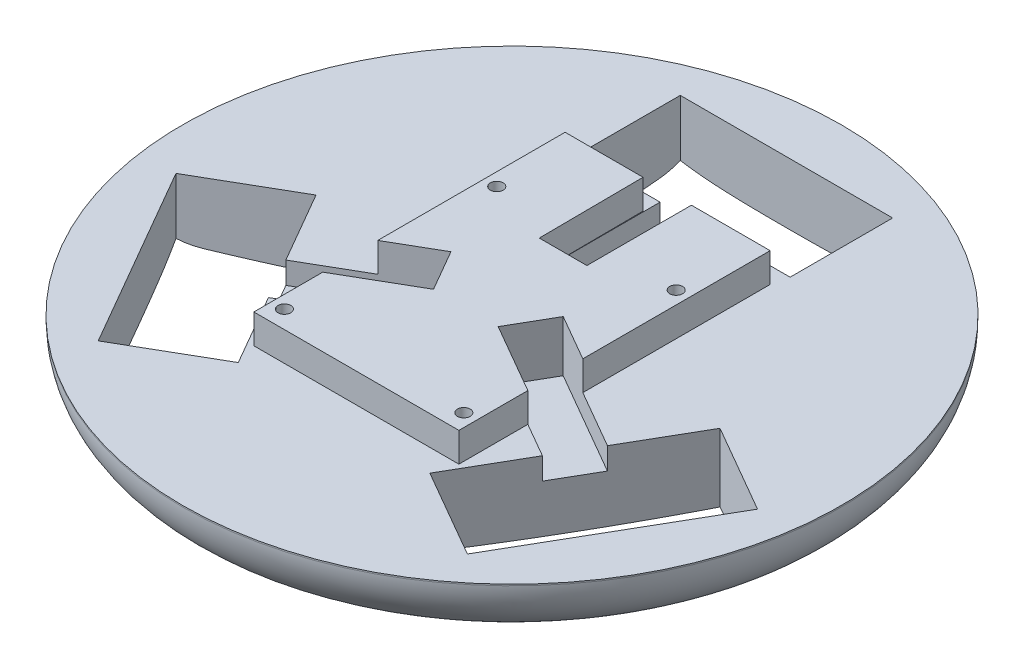
SolidWorks part; units mm, degrees
ref_plane "Front Plane" through (0, 0, 0) normal (0, 0, 1) x (1, 0, 0)
ref_plane "Top Plane" through (0, 0, 0) normal (0, 1, 0) x (1, 0, 0)
ref_plane "Right Plane" through (0, 0, 0) normal (1, 0, 0) x (0, 0, -1)
sketch "Sketch2" plane through (0, 0, 0) normal (0, 1, 0) x (1, 0, 0)
  line L0 (0, -68.0098) -> (0, 65.7503) construction
  line L1 (-29, 74.9495) -> (29, 74.9495)
  line L2 (-29, 74.9495) -> (-29, 46.9495)
  line L3 (-29, 46.9495) -> (29, 46.9495)
  line L4 (29, 74.9495) -> (29, 46.9495)
  line L5 (-29, 74.9495) -> (29, 46.9495) construction
  line L6 (-29, 46.9495) -> (29, 74.9495) construction
  line L7 (-70.2148, 0) -> (95.7201, 0) construction
  line L8 (0, 0) -> (-72.5813, -41.9048) construction
  line L9 (0, 0) -> (72.5813, -41.9048) construction
  line L10 (79.4081, -12.36) -> (50.4081, -62.5895)
  line L11 (55.1594, 1.64) -> (26.1594, -48.5895)
  line L12 (79.4081, -12.36) -> (55.1594, 1.64)
  line L13 (50.4081, -62.5895) -> (26.1594, -48.5895)
  line L14 (-50.4081, -62.5895) -> (-79.4081, -12.36)
  line L15 (-26.1594, -48.5895) -> (-55.1594, 1.64)
  line L16 (-50.4081, -62.5895) -> (-26.1594, -48.5895)
  line L17 (-79.4081, -12.36) -> (-55.1594, 1.64)
  line L18 (-6.5, -8.0505) -> (6.5, 46.9495) construction
  line L19 (-6.5, 46.9495) -> (6.5, 46.9495)
  line L20 (-6.5, 46.9495) -> (-6.5, -8.0505)
  line L21 (-6.5, -8.0505) -> (6.5, -8.0505)
  line L22 (6.5, 46.9495) -> (6.5, -8.0505)
  line L23 (-6.5, 46.9495) -> (6.5, -8.0505) construction
  line L24 (31.4023, -15.1408) -> (6.5, -0.7634)
  line L25 (-6.1216, -8.0505) -> (0, 2.5524)
  line L26 (24.9023, -26.3991) -> (0, -12.0218)
  line L27 (-25.0514, -26.4852) -> (0, -12.0218)
  line L28 (0, 2.5524) -> (6.1216, -8.0505)
  line L29 (-33.4324, -16.3129) -> (-6.5, -0.7634)
  circle A2 centre (0, 0) radius 16 construction
  point P3 (0, 19.4495)
  point P4 (0, 46.9495)
  point P6 (0, 60.9495)
  point P13 (0, 0)
  point P33 (0, 0)
  point P41 (0, -4.5162)
  dimension "D1" = 55
  dimension "D2" = 13
  dimension "D3" = 32
  dimension "D5" = 58
  dimension "D6" = 120
  dimension "D7" = 28
  dimension "D8" = 3
  dimension "D4" = 3
sketch "Sketch3" plane through (0, 0, 0) normal (1, 0, 0) x (0, 0, -1)
  line L0 (0, 83.7838) -> (0, -101.0811) construction
  line L1 (-115.9459, 0) -> (127.2973, 0) construction
  line L3 (90, 19.6135) -> (90, 20)
  line L5 (0, 20) -> (0, 0)
  line L6 (90, 20) -> (0, 20)
  arc A0 (0, 0) -> (75.2808, 3.2098) centre (13.1832, 575.2021) ccw
  arc A2 (90, 19.6135) -> (75.2808, 3.2098) centre (73.5, 19.6135) cw
  point P13 (90, 5)
  dimension "D5" = 16.5
  dimension "D1" = 15
  dimension "D2" = 20
  dimension "D3" = 20
  dimension "D4" = 90
revolve "Revolve1" add sketch "Sketch3" angle 360 about L5
extrude "Cut-Extrude1" cut sketch "Sketch2" along normal blind 40 contours L3 L4 L1 L2 | L15 L17 L14 L16 | L11 L13 L10 L12
sketch "Sketch4" plane through (0, 20, 0) normal (0, 1, 0) x (1, 0, 0)
  line L1 (-6.5, 46.9495) -> (6.5, 46.9495)
  line L2 (-6.5, 46.9495) -> (-6.5, 13.9495)
  line L3 (-6.5, 13.9495) -> (6.5, 13.9495)
  line L4 (6.5, 46.9495) -> (6.5, 13.9495)
  line L5 (-6.5, 46.9495) -> (6.5, 13.9495) construction
  line L6 (-6.5, 13.9495) -> (6.5, 46.9495) construction
  line L7 (43.9094, -17.8456) -> (37.4094, -29.1039)
  line L8 (-55.1594, 1.64) -> (-26.1594, -48.5895) construction
  line L9 (-29, 46.9495) -> (29, 46.9495) construction
  line L10 (55.1594, 1.64) -> (26.1594, -48.5895) construction
  line L26 (43.9094, -17.8456) -> (15.3306, -1.3456)
  line L27 (37.4094, -29.1039) -> (8.8306, -12.6039)
  line L28 (15.3306, -1.3456) -> (8.8306, -12.6039)
  line L29 (-37.4094, -29.1039) -> (-43.9094, -17.8456)
  line L30 (-37.4094, -29.1039) -> (-8.8306, -12.6039)
  line L31 (-43.9094, -17.8456) -> (-15.3306, -1.3456)
  line L32 (-8.8306, -12.6039) -> (-15.3306, -1.3456)
  point P0 (0, 30.4495)
  point P5 (0, 46.9495)
  point P22 (0, 0)
  point P23 (0, 4.0327)
  point P32 (-2.3282, 4.0326)
  line M8 (-55.1594, 1.64) -> (-26.1594, -48.5895)
  line M13 (26.1594, -48.5895) -> (55.1594, 1.64)
  line M17 (29, 46.9495) -> (-29, 46.9495)
  dimension "D1" = 13
  dimension "D2" = 33
extrude "Cut-Extrude2" cut sketch "Sketch4" against normal blind 6 contours L4 L2 L3 M17 | L30 L32 L31 M8 | L26 L28 L27 M13 region at (0, 20, -30.4495) region at (26.37, 20, 15.2247) region at (-26.37, 20, 15.2247)
sketch "Sketch5" plane through (0, 20, 0) normal (0, 1, 0) x (1, 0, 0)
  line L0 (-28, -23.6714) -> (-8.8306, -12.6039)
  line L1 (-28, 42.5) -> (-6.7113, 42.5)
  line L2 (-28, 42.5) -> (-28, -8.6603)
  line L3 (-28, -42.5) -> (28, -42.5)
  line L4 (28, 42.5) -> (28, -8.6603)
  line L5 (-28, 42.5) -> (28, -42.5) construction
  line L6 (-28, -42.5) -> (28, 42.5) construction
  line L7 (-37.4094, -29.1039) -> (-8.8306, -12.6039) construction
  line L8 (-8.8306, -12.6039) -> (-15.3306, -1.3456)
  line L9 (-15.3306, -1.3456) -> (-28, -8.6603)
  line L10 (-43.9094, -17.8456) -> (-15.3306, -1.3456) construction
  line L11 (28, -23.6714) -> (8.8306, -12.6039)
  line L12 (37.4094, -29.1039) -> (8.8306, -12.6039) construction
  line L13 (8.8306, -12.6039) -> (15.3306, -1.3456)
  line L14 (15.3306, -1.3456) -> (28, -8.6603)
  line L15 (-6.7113, 42.5) -> (-6.5, 13.9495)
  line L16 (-6.5, 13.9495) -> (6.5, 13.9495)
  line L17 (6.5, 13.9495) -> (6.5, 42.5)
  line L18 (6.5, 46.9495) -> (6.5, 13.9495) construction
  line L19 (6.5, 46.9495) -> (6.5, 13.9495) construction
  line L20 (-28, -23.6714) -> (-28, -42.5)
  line L21 (28, -23.6714) -> (28, -42.5)
  line L22 (6.5, 42.5) -> (28, 42.5)
  line L23 (0, 13.9495) -> (0, -42.8187) construction
  line L24 (-28, -8.6603) -> (28, -8.6603) construction
  circle A0 centre (-24.5, -37.6603) radius 1.75
  circle A1 centre (24.5, -37.6603) radius 1.75
  circle A2 centre (24.5, 20.3397) radius 1.75
  circle A3 centre (-24.5, 20.3397) radius 1.75
  point P0 (0, 0)
  point P44 (0, 0)
  point P45 (0, 0)
  dimension "D3" = 3.5
  dimension "D1" = 56
  dimension "D2" = 85
  dimension "D4" = 49
  dimension "D5" = 58
extrude "Boss-Extrude1" add sketch "Sketch5" along normal blind 8
